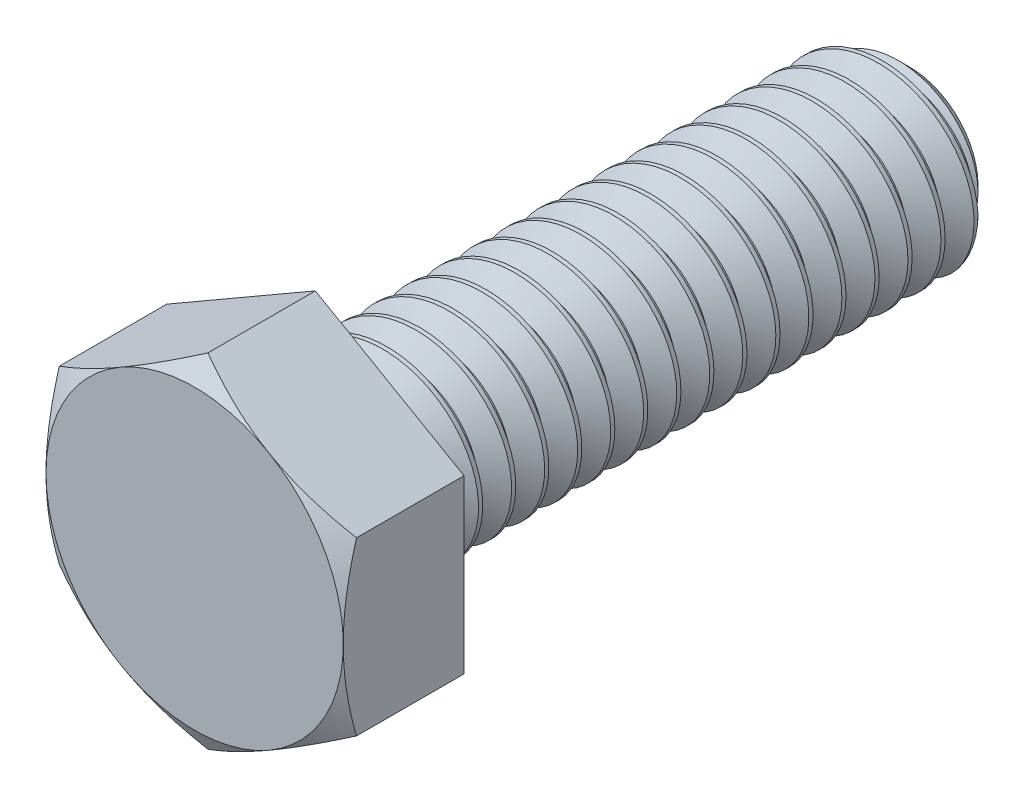
SolidWorks part; units mm, degrees
ref_plane "Front Plane" through (0, 0, 0) normal (0, 0, 1) x (1, 0, 0)
ref_plane "Top Plane" through (0, 0, 0) normal (0, 1, 0) x (1, 0, 0)
ref_plane "Right Plane" through (0, 0, 0) normal (1, 0, 0) x (0, 0, -1)
sketch "Sketch1" plane through (0, 0, 0) normal (1, 0, 0) x (0, 0, -1)
  line L0 (0, 0) -> (25.4, 0) construction
  line L1 (25.4, 3.9688) -> (25.4, -3.9688) construction
  line L2 (0, 6.35) -> (0, -6.35) construction
  line L3 (0, 0) -> (-5.1594, 0) construction
  line L4 (-5.1594, 6.35) -> (-5.1594, -6.35) construction
  line L5 (25.3118, 4.1215) -> (26.7229, 4.1215) construction
  line L6 (26.7229, 4.1215) -> (26.0174, 2.8994) construction
  line L7 (26.0174, 2.8994) -> (25.3118, 4.1215) construction
  line L8 (25.3559, 4.0451) -> (26.6788, 4.0451) construction
  line L9 (25.4, 3.9688) -> (26.6347, 3.9688) construction
  line L10 (25.9292, 3.0522) -> (26.1056, 3.0522) construction
  line L11 (26.0174, 4.1215) -> (26.0174, 3.9688) construction
  line L12 (26.0174, 3.0522) -> (26.0174, 2.8994) construction
  point P5 (25.4, 0)
  point P9 (0, 0)
  point P13 (-5.1594, 0)
  point P18 (21.8722, -3.9688)
  point P25 (26.0174, 4.0451)
  dimension "Length" = 25.4
  dimension "Thread OD" = 7.9375
  dimension "Hex Width" = 12.7
  dimension "Hex Height" = 5.1594
  dimension "D1" = 60
  dimension "Pitch" = 1.4111
  dimension "D2" = 0.1764
  dimension "D3" = 3.5278
sketch "Sketch2" plane through (0, 0, 0) normal (1, 0, 0) x (0, 0, -1)
  line L0 (0, 0) -> (25.4, 0)
  line L1 (0, 6.35) -> (0, -6.35) construction
  line L2 (25.4, 0) -> (25.4, 3.9688)
  line L3 (25.4, 3.9688) -> (0, 3.9687)
  line L4 (0, 3.9687) -> (0, 0)
revolve "Revolve1" add sketch "Sketch2" angle 360 about L0
sketch "Sketch3" plane through (0, 0, 0) normal (0, 0, 1) x (1, 0, 0)
  line L1 (0, 7.3323) -> (-6.35, 3.6662)
  line L2 (-6.35, 3.6662) -> (-6.35, -3.6662)
  line L3 (-6.35, -3.6662) -> (0, -7.3323)
  line L4 (0, -7.3323) -> (6.35, -3.6662)
  line L5 (6.35, -3.6662) -> (6.35, 3.6662)
  line L6 (6.35, 3.6662) -> (0, 7.3323)
  circle A0 centre (0, 0) radius 6.35 construction
extrude "Boss-Extrude1" add sketch "Sketch3" along normal up to vertex (5.1594 mm away) up to point (0, 0, 5.1594)
chamfer "Chamfer1" distance 1.0583 angle 45 1 edges at (3.9688, 0, -25.4)
sketch "Sketch4" plane through (0, 0, 5.1594) normal (0, 0, 1) x (1, 0, 0)
  circle A0 centre (0, 0) radius 6.35
extrude "Cut-Extrude1" cut sketch "Sketch4" against normal through all draft 60 flip side to cut
ref_axis "Center Axis 1" through (0, 0, -68.7678) along (0, 0, 1)
split "Split1" bodies to split 106 resulting bodies 107 108 split by face at (3.9687, 0, 0)
sketch "Sketch5" plane through (0, 0, 0) normal (1, 0, 0) x (0, 0, -1)
  line L0 (25.3559, 4.0451) -> (26.6788, 4.0451)
  line L1 (25.3559, 4.0451) -> (25.9292, 3.0522)
  line L2 (25.9292, 3.0522) -> (26.1056, 3.0522)
  line L3 (26.6788, 4.0451) -> (26.1056, 3.0522)
sketch "Sketch6" plane through (0, 0, -25.4) normal (0, 0, -1) x (-1, 0, 0)
  circle A0 centre (0, 0) radius 3.9688
curve "Helix/Spiral1" pitch 1.4111 height 26.8111 radius 3.9688 centre (0, 0, -25.4) axis (0, 0, 1) start towards (0, 1, 0)
sweep "Cut-Sweep1" cut profiles "Sketch5" path "Helix/Spiral1" align with end faces yes
combine bodies "Combine1" operation type add bodies to combine 108 109
equation "\"D2@Sketch1\"=\"Pitch@Sketch1\"/8"
equation "\"D1@Chamfer1\"=\"Pitch@Sketch1\"*.75"
equation "\"D4@Helix/Spiral1\"=\"Pitch@Sketch1\""
equation "\"D3@Helix/Spiral1\"=\"Length@Sketch1\"+\"Pitch@Sketch1\""
equation "\"D3@Sketch1\"=\"Pitch@Sketch1\"*2.5"
